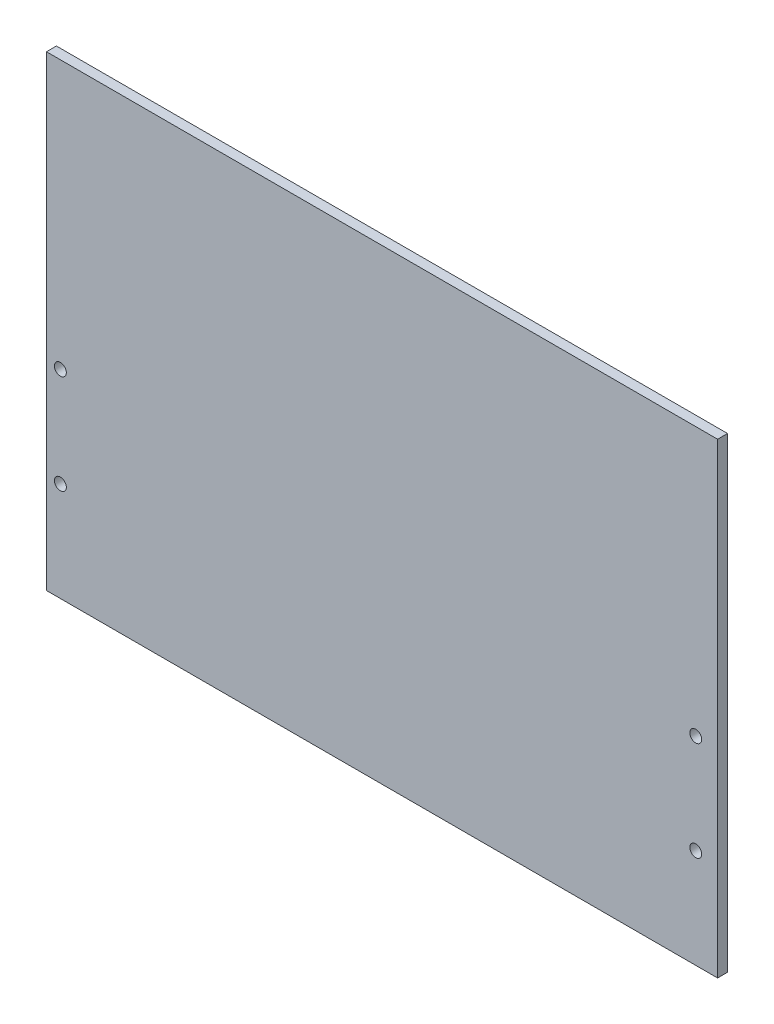
SolidWorks part; units mm, degrees
ref_plane "Front Plane" through (0, 0, 0) normal (0, 0, 1) x (1, 0, 0)
ref_plane "Top Plane" through (0, 0, 0) normal (0, 1, 0) x (1, 0, 0)
ref_plane "Right Plane" through (0, 0, 0) normal (1, 0, 0) x (0, 0, -1)
sketch "Sketch1" plane through (0, 0, 0) normal (0, 0, 1) x (1, 0, 0)
  line L0 (0, 117.5) -> (0, -117.5) construction
  line L1 (-169, -117.5) -> (169, -117.5)
  line L2 (-169, -117.5) -> (-169, 117.5)
  line L3 (-169, 117.5) -> (169, 117.5)
  line L4 (169, -117.5) -> (169, 117.5)
  line L5 (-169, -117.5) -> (169, 117.5) construction
  line L6 (-169, 117.5) -> (169, -117.5) construction
  circle A0 centre (-162, -67.5) radius 3
  circle A1 centre (-162, -17.5) radius 3
  circle A4 centre (158, -17.5) radius 3
  circle A5 centre (158, -67.5) radius 3
  point P0 (0, 0)
  point P10 (0, 0)
  point P17 (0, 0)
  point P18 (161, -17.5)
  point P19 (161, -17.5)
  point P20 (161, -17.5)
  point P21 (0, 0)
  point P24 (51.7656, -87.7403)
  dimension "D6" = 6
  dimension "D1" = 338
  dimension "D2" = 235
  dimension "D3" = 50
  dimension "D4" = 50
  dimension "D5" = 7
  dimension "D7" = 50
  dimension "D8" = 50
  dimension "D9" = 11
extrude "Boss-Extrude1" add sketch "Sketch1" along normal blind 5
